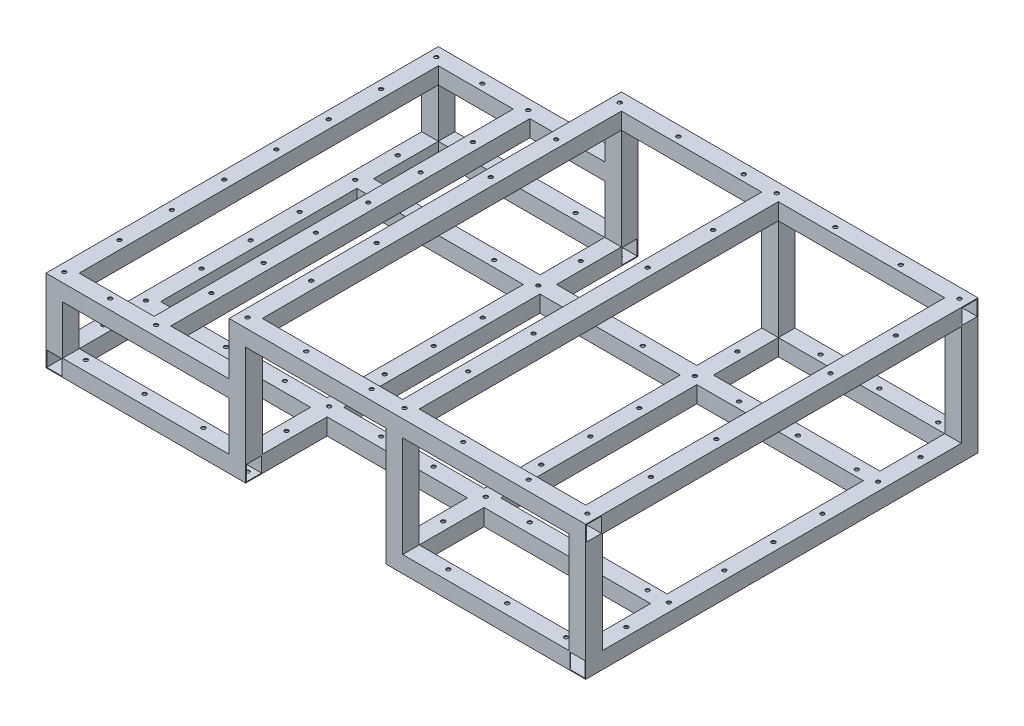
SolidWorks part; units mm, degrees
ref_plane "Front Plane" through (0, 0, 0) normal (0, 0, 1) x (1, 0, 0)
ref_plane "Top Plane" through (0, 0, 0) normal (0, 1, 0) x (1, 0, 0)
ref_plane "Right Plane" through (0, 0, 0) normal (1, 0, 0) x (0, 0, -1)
sketch "Sketch1" plane through (0, 0, 0) normal (0, 1, 0) x (1, 0, 0)
  line L0 (0, 0) -> (-415.7612, 0) construction
  line L1 (-387.3, -150) -> (387.3, -150)
  line L2 (-387.3, -150) -> (-387.3, -175.4)
  line L3 (-387.3, -175.4) -> (387.3, -175.4)
  line L4 (387.3, -150) -> (387.3, -175.4)
  line L9 (0, 0) -> (0, -321.173) construction
  line L10 (387.3, 150) -> (387.3, 175.4)
  line L11 (-387.3, 175.4) -> (387.3, 175.4)
  line L12 (-387.3, 150) -> (-387.3, 175.4)
  line L13 (-387.3, 150) -> (387.3, 150)
  point P7 (0, -175.4)
  dimension "D1" = 774.6
  dimension "D2" = 25.4
  dimension "D3" = 150
  dimension "D4" = 0
extrude "Boss-Extrude1" add sketch "Sketch1" along normal blind 25.4
sketch "Sketch4" plane through (-387.3, 0, 0) normal (-1, 0, 0) x (0, 0, 1)
  line L0 (-175.4, 25.4) -> (-150, 25.4) construction
  line L1 (-174.2, 24.2) -> (-151.2, 24.2)
  line L2 (-174.2, 24.2) -> (-174.2, 1.2)
  line L3 (-174.2, 1.2) -> (-151.2, 1.2)
  line L4 (-151.2, 24.2) -> (-151.2, 1.2)
  line L5 (-150, 25.4) -> (-150, 0) construction
  line L6 (-175.4, 0) -> (-150, 0) construction
  line L7 (-175.4, 25.4) -> (-175.4, 0) construction
  line L8 (0, 0) -> (0, 21.4103) construction
  line L9 (174.2, 1.2) -> (151.2, 1.2)
  line L10 (151.2, 24.2) -> (151.2, 1.2)
  line L11 (174.2, 24.2) -> (151.2, 24.2)
  line L12 (174.2, 24.2) -> (174.2, 1.2)
  dimension "D1" = 1.2
  dimension "D2" = 1.2
  dimension "D3" = 1.2
  dimension "D4" = 1.2
extrude "Cut-Extrude2" cut sketch "Sketch4" against normal up to next (774.6 mm away)
sketch "Sketch2" plane through (0, 0, 0) normal (0, -1, 0) x (1, 0, 0)
  line L0 (0, 0) -> (0, -349.2287) construction
  line L1 (412.7, 300) -> (387.3, 300)
  line L2 (412.7, 300) -> (412.7, -300)
  line L3 (412.7, -300) -> (387.3, -300)
  line L4 (387.3, 300) -> (387.3, -300)
  line L5 (0, 0) -> (432.1136, 0) construction
  line L6 (387.3, -150) -> (387.3, -175.4) construction
  line L7 (-387.3, 300) -> (-387.3, -300)
  line L8 (-412.7, -300) -> (-387.3, -300)
  line L9 (-412.7, 300) -> (-412.7, -300)
  line L10 (-412.7, 300) -> (-387.3, 300)
  point P10 (387.3, 0)
  dimension "D1" = 25.4
  dimension "D2" = 600
  dimension "D3" = 25.4
  dimension "D4" = 0
extrude "Boss-Extrude2" add sketch "Sketch2" against normal blind 25.4
sketch "Sketch3" plane through (0, 0, -300) normal (0, 0, -1) x (-1, 0, 0)
  line L0 (-387.3, 25.4) -> (-412.7, 25.4) construction
  line L1 (-411.5, 24.2) -> (-388.5, 24.2)
  line L2 (-411.5, 24.2) -> (-411.5, 1.2)
  line L3 (-411.5, 1.2) -> (-388.5, 1.2)
  line L4 (-388.5, 24.2) -> (-388.5, 1.2)
  line L5 (-387.3, 25.4) -> (-387.3, 0) construction
  line L6 (-387.3, 0) -> (-412.7, 0) construction
  line L7 (-412.7, 25.4) -> (-412.7, 0) construction
  line L8 (0, 0) -> (0, 119.739) construction
  line L9 (388.5, 24.2) -> (388.5, 1.2)
  line L10 (411.5, 1.2) -> (388.5, 1.2)
  line L11 (411.5, 24.2) -> (411.5, 1.2)
  line L12 (411.5, 24.2) -> (388.5, 24.2)
  point P10 (-400, 0)
  dimension "D1" = 1.2
  dimension "D2" = 1.2
  dimension "D3" = 1.2
  dimension "D4" = 1.2
extrude "Cut-Extrude1" cut sketch "Sketch3" against normal up to next
sketch "Sketch6" plane through (-387.3, 0, 0) normal (1, 0, 0) x (0, 0, -1)
  line L0 (300, 0) -> (175.4, 0) construction
  line L1 (300, 25.4) -> (274.6, 25.4)
  line L2 (300, 25.4) -> (300, 0)
  line L3 (300, 0) -> (274.6, 0)
  line L4 (274.6, 25.4) -> (274.6, 0)
  line L5 (0, 0) -> (0, 25.4) construction
  line L6 (150, 0) -> (-150, 0) construction
  line L7 (150, 25.4) -> (-150, 25.4) construction
  line L13 (-274.6, 25.4) -> (-274.6, 0)
  line L14 (-300, 0) -> (-274.6, 0)
  line L15 (-300, 25.4) -> (-300, 0)
  line L16 (-300, 25.4) -> (-274.6, 25.4)
  dimension "D1" = 25.4
extrude "Boss-Extrude3" add sketch "Sketch6" along normal blind 280
sketch "Sketch7" plane through (387.3, 0, 0) normal (-1, 0, 0) x (0, 0, 1)
  line L0 (-175.4, 25.4) -> (-300, 25.4) construction
  line L1 (-300, 0) -> (-274.6, 0)
  line L2 (-300, 0) -> (-300, 25.4)
  line L3 (-300, 25.4) -> (-274.6, 25.4)
  line L4 (-274.6, 0) -> (-274.6, 25.4)
  line L10 (0, 0) -> (0, 25.4) construction
  line L11 (150, 0) -> (-150, 0) construction
  line L12 (150, 25.4) -> (-150, 25.4) construction
  line L13 (274.6, 0) -> (274.6, 25.4)
  line L14 (300, 25.4) -> (274.6, 25.4)
  line L15 (300, 0) -> (300, 25.4)
  line L16 (300, 0) -> (274.6, 0)
  dimension "D1" = 25.4
extrude "Boss-Extrude4" add sketch "Sketch7" along normal blind 280
ref_plane "Plane1" through (0, 0, 0) normal (1, 0, 0) x (0, 0, -1)
sketch "Sketch8" plane through (0, 0, 0) normal (1, 0, 0) x (0, 0, -1)
  line L4 (-275.8, 24.2) -> (-298.8, 24.2)
  line L5 (-298.8, 24.2) -> (-298.8, 1.2)
  line L6 (-298.8, 1.2) -> (-275.8, 1.2)
  line L7 (-275.8, 1.2) -> (-275.8, 24.2)
  line L8 (-274.6, 25.4) -> (-300, 25.4)
  line L9 (-300, 25.4) -> (-300, 0)
  line L10 (-300, 0) -> (-274.6, 0)
  line L11 (-274.6, 0) -> (-274.6, 25.4)
  line L12 (-274.6, 25.4) -> (-300, 25.4)
  line L13 (-300, 25.4) -> (-300, 0)
  line L14 (-300, 0) -> (-274.6, 0)
  line L15 (-274.6, 0) -> (-274.6, 25.4)
  line L16 (300, 0) -> (300, 25.4)
  line L17 (300, 25.4) -> (274.6, 25.4)
  line L18 (274.6, 25.4) -> (274.6, 0)
  line L19 (274.6, 0) -> (300, 0)
  line L20 (300, 0) -> (300, 25.4)
  line L21 (300, 25.4) -> (274.6, 25.4)
  line L22 (274.6, 25.4) -> (274.6, 0)
  line L23 (274.6, 0) -> (300, 0)
  line L24 (298.8, 1.2) -> (298.8, 24.2)
  line L25 (298.8, 24.2) -> (275.8, 24.2)
  line L26 (275.8, 24.2) -> (275.8, 1.2)
  line L27 (275.8, 1.2) -> (298.8, 1.2)
  dimension "D1" = 0
  dimension "D2" = 0
  dimension "D3" = 1.2
  dimension "D4" = 1.2
extrude "Cut-Extrude4" cut sketch "Sketch8" against normal up to surface (388.5 mm away) and the other way up to vertex (388.5 mm away) contours L24 L25 L26 L27 | L7 L4 L5 L6 up to face at (-388.5, 12.7, 0) other way up to point (388.5, 1.2, 300)
sketch "Sketch9" plane through (0, 0, -274.6) normal (0, 0, 1) x (1, 0, 0)
  line L0 (-107.3, 25.4) -> (-387.3, 25.4) construction
  line L1 (-107.3, 0) -> (-132.7, 0)
  line L2 (-107.3, 0) -> (-107.3, 25.4)
  line L3 (-107.3, 25.4) -> (-132.7, 25.4)
  line L4 (-132.7, 0) -> (-132.7, 25.4)
  line L5 (-107.3, 0) -> (107.3, 0) construction
  line L6 (-107.3, 25.4) -> (107.3, 25.4) construction
  line L7 (0, 25.4) -> (0, 0) construction
  line L12 (-108.5, 1.2) -> (-131.5, 1.2)
  line L13 (-131.5, 1.2) -> (-131.5, 24.2)
  line L14 (-108.5, 24.2) -> (-131.5, 24.2)
  line L15 (-108.5, 1.2) -> (-108.5, 24.2)
  line L16 (108.5, 1.2) -> (108.5, 24.2)
  line L17 (108.5, 24.2) -> (131.5, 24.2)
  line L18 (107.3, 25.4) -> (132.7, 25.4)
  line L19 (107.3, 0) -> (107.3, 25.4)
  line L20 (131.5, 1.2) -> (131.5, 24.2)
  line L21 (108.5, 1.2) -> (131.5, 1.2)
  line L22 (132.7, 0) -> (132.7, 25.4)
  line L23 (107.3, 0) -> (132.7, 0)
  dimension "D1" = 25.4
  dimension "D2" = 1.2
extrude "Boss-Extrude5" add sketch "Sketch9" along normal up to surface (550.4 mm away) up to face at (-247.9, 12.7, 275.8)
sketch "Sketch11" plane through (0, 25.4, 0) normal (0, 1, 0) x (1, 0, 0)
  line L0 (-412.7, 0) -> (0, 0) construction
  line L1 (-412.7, 300) -> (-387.3, 300)
  line L2 (-412.7, 300) -> (-412.7, 274.6)
  line L3 (-412.7, 274.6) -> (-387.3, 274.6)
  line L4 (-387.3, 300) -> (-387.3, 274.6)
  line L5 (-412.7, -300) -> (-412.7, 300) construction
  line L7 (-411.5, 298.8) -> (-388.5, 298.8)
  line L8 (-388.5, 298.8) -> (-388.5, 275.8)
  line L9 (-411.5, 275.8) -> (-388.5, 275.8)
  line L10 (-411.5, 298.8) -> (-411.5, 275.8)
  line L11 (-411.5, -298.8) -> (-411.5, -275.8)
  line L12 (-411.5, -275.8) -> (-388.5, -275.8)
  line L13 (-388.5, -298.8) -> (-388.5, -275.8)
  line L14 (-411.5, -298.8) -> (-388.5, -298.8)
  line L15 (-387.3, -300) -> (-387.3, -274.6)
  line L16 (-412.7, -274.6) -> (-387.3, -274.6)
  line L17 (-412.7, -300) -> (-412.7, -274.6)
  line L18 (-412.7, -300) -> (-387.3, -300)
  dimension "D1" = 1.2
extrude "Boss-Extrude6" add sketch "Sketch11" along normal blind 74.6
sketch "Sketch12" plane through (0, 25.4, 0) normal (0, 1, 0) x (1, 0, 0)
  line L0 (-108.5, 298.8) -> (-131.5, 298.8)
  line L1 (-107.3, 300) -> (-132.7, 300)
  line L2 (-107.3, 300) -> (-107.3, 274.6)
  line L3 (-107.3, 274.6) -> (-132.7, 274.6)
  line L4 (-132.7, 300) -> (-132.7, 274.6)
  line L5 (-131.5, 298.8) -> (-131.5, 275.8)
  line L6 (-108.5, 275.8) -> (-131.5, 275.8)
  line L7 (-108.5, 298.8) -> (-108.5, 275.8)
  line L8 (-132.7, 0) -> (412.7, 0) construction
  line L10 (-132.7, -150) -> (-132.7, 150) construction
  line L11 (412.7, 300) -> (412.7, -300) construction
  line L12 (140, 0) -> (140, 300) construction
  line L13 (107.3, 300) -> (412.7, 300) construction
  line L14 (-108.5, -298.8) -> (-108.5, -275.8)
  line L15 (-108.5, -275.8) -> (-131.5, -275.8)
  line L16 (-131.5, -298.8) -> (-131.5, -275.8)
  line L17 (-132.7, -300) -> (-132.7, -274.6)
  line L18 (-107.3, -274.6) -> (-132.7, -274.6)
  line L19 (-107.3, -300) -> (-107.3, -274.6)
  line L20 (-107.3, -300) -> (-132.7, -300)
  line L21 (-108.5, -298.8) -> (-131.5, -298.8)
  line L22 (388.5, -298.8) -> (411.5, -298.8)
  line L23 (387.3, -300) -> (412.7, -300)
  line L24 (387.3, -300) -> (387.3, -274.6)
  line L25 (387.3, -274.6) -> (412.7, -274.6)
  line L26 (412.7, -300) -> (412.7, -274.6)
  line L27 (411.5, -298.8) -> (411.5, -275.8)
  line L28 (388.5, -275.8) -> (411.5, -275.8)
  line L29 (388.5, -298.8) -> (388.5, -275.8)
  line L30 (388.5, 298.8) -> (388.5, 275.8)
  line L31 (388.5, 275.8) -> (411.5, 275.8)
  line L32 (411.5, 298.8) -> (411.5, 275.8)
  line L33 (412.7, 300) -> (412.7, 274.6)
  line L34 (387.3, 274.6) -> (412.7, 274.6)
  line L35 (387.3, 300) -> (387.3, 274.6)
  line L36 (387.3, 300) -> (412.7, 300)
  line L37 (388.5, 298.8) -> (411.5, 298.8)
  line L38 (132.7, 274.6) -> (387.3, 274.6) construction
  line L39 (107.3, 300) -> (132.7, 300)
  line L40 (107.3, 300) -> (107.3, 274.6)
  line L41 (107.3, 274.6) -> (132.7, 274.6)
  line L42 (132.7, 300) -> (132.7, 274.6)
  line L47 (108.5, 298.8) -> (131.5, 298.8)
  line L48 (131.5, 298.8) -> (131.5, 275.8)
  line L49 (108.5, 275.8) -> (131.5, 275.8)
  line L50 (108.5, 298.8) -> (108.5, 275.8)
  line L51 (108.5, -298.8) -> (108.5, -275.8)
  line L52 (108.5, -275.8) -> (131.5, -275.8)
  line L53 (131.5, -298.8) -> (131.5, -275.8)
  line L54 (108.5, -298.8) -> (131.5, -298.8)
  line L55 (132.7, -300) -> (132.7, -274.6)
  line L56 (107.3, -274.6) -> (132.7, -274.6)
  line L57 (107.3, -300) -> (107.3, -274.6)
  line L58 (107.3, -300) -> (132.7, -300)
  line L59 (107.3, 175.4) -> (107.3, 300) construction
  point P12 (387.3, 287.3)
  dimension "D2" = 0
  dimension "D3" = 25.4
  dimension "D5" = 254.6
  dimension "D6" = 214.6
  dimension "D1" = 1.2
  dimension "D4" = 1.2
extrude "Boss-Extrude7" add sketch "Sketch12" along normal blind 154.6
sketch "Sketch13" plane through (0, 180, 0) normal (0, 1, 0) x (1, 0, 0)
  line L0 (-107.3, 274.6) -> (-107.3, -274.6) construction
  line L1 (-132.7, -300) -> (412.7, -300)
  line L2 (-132.7, -300) -> (-132.7, -274.6)
  line L3 (-132.7, -274.6) -> (412.7, -274.6)
  line L4 (412.7, -300) -> (412.7, -274.6)
  line L5 (-107.3, 0) -> (0, 0) construction
  line L6 (412.7, 300) -> (412.7, 274.6)
  line L7 (-132.7, 274.6) -> (412.7, 274.6)
  line L8 (-132.7, 300) -> (-132.7, 274.6)
  line L9 (-132.7, 300) -> (412.7, 300)
extrude "Boss-Extrude9" add sketch "Sketch13" along normal blind 25.4
sketch "Sketch14" plane through (-132.7, 0, 0) normal (-1, 0, 0) x (0, 0, 1)
  line L0 (-300, 205.4) -> (-274.6, 205.4) construction
  line L1 (-298.8, 204.2) -> (-275.8, 204.2)
  line L2 (-298.8, 204.2) -> (-298.8, 181.2)
  line L3 (-298.8, 181.2) -> (-275.8, 181.2)
  line L4 (-275.8, 204.2) -> (-275.8, 181.2)
  line L5 (-300, 205.4) -> (-300, 25.4) construction
  line L6 (-274.6, 205.4) -> (-274.6, 25.4) construction
  line L7 (-300, 180) -> (-274.6, 180) construction
  line L8 (-274.6, 180) -> (274.6, 180) construction
  line L9 (274.6, 205.4) -> (274.6, 25.4) construction
  line L10 (0, 180) -> (0, 204.2) construction
  line L11 (300, 180) -> (274.6, 180) construction
  line L12 (275.8, 204.2) -> (275.8, 181.2)
  line L13 (298.8, 181.2) -> (275.8, 181.2)
  line L14 (298.8, 204.2) -> (298.8, 181.2)
  line L15 (298.8, 204.2) -> (275.8, 204.2)
  dimension "D1" = 1.2
  dimension "D2" = 1.2
  dimension "D3" = 1.2
  dimension "D4" = 25.4
  dimension "D5" = 1.2
extrude "Cut-Extrude5" cut sketch "Sketch14" against normal up to surface (545.4 mm away)
sketch "Sketch15" plane through (0, 0, -274.6) normal (0, 0, 1) x (1, 0, 0)
  line L27 (107.3, 180) -> (132.7, 180)
  line L28 (132.7, 180) -> (132.7, 205.4)
  line L29 (-132.7, 205.4) -> (412.7, 205.4) construction
  line L30 (132.7, 205.4) -> (107.3, 205.4)
  line L31 (107.3, 205.4) -> (107.3, 180)
  line L32 (108.5, 181.2) -> (131.5, 181.2)
  line L33 (131.5, 181.2) -> (131.5, 204.2)
  line L34 (131.5, 204.2) -> (108.5, 204.2)
  line L35 (108.5, 204.2) -> (108.5, 181.2)
  line L36 (-107.3, 180) -> (-107.3, 25.4) construction
  line L37 (-132.7, 205.4) -> (-107.3, 205.4)
  line L38 (-132.7, 205.4) -> (-132.7, 180)
  line L39 (-132.7, 180) -> (-107.3, 180)
  line L40 (-107.3, 205.4) -> (-107.3, 180)
  line L41 (-131.5, 204.2) -> (-108.5, 204.2)
  line L42 (412.7, 205.4) -> (387.3, 205.4)
  line L43 (412.7, 205.4) -> (412.7, 180)
  line L44 (412.7, 180) -> (387.3, 180)
  line L45 (387.3, 205.4) -> (387.3, 180)
  line L46 (-108.5, 204.2) -> (-108.5, 181.2)
  line L47 (-131.5, 181.2) -> (-108.5, 181.2)
  line L48 (-131.5, 204.2) -> (-131.5, 181.2)
  line L49 (411.5, 204.2) -> (388.5, 204.2)
  line L50 (388.5, 204.2) -> (388.5, 181.2)
  line L51 (411.5, 181.2) -> (388.5, 181.2)
  line L52 (411.5, 204.2) -> (411.5, 181.2)
  dimension "D2" = 1.2
  dimension "D1" = 1.2
extrude "Boss-Extrude10" add sketch "Sketch15" along normal up to surface (549.2 mm away) up to face at (260, 12.7, 274.6)
sketch "Sketch16" plane through (-412.7, 0, 0) normal (-1, 0, 0) x (0, 0, 1)
  line L0 (275.8, 101.2) -> (298.8, 101.2)
  line L1 (274.6, 100) -> (300, 100)
  line L2 (274.6, 100) -> (274.6, 125.4)
  line L3 (274.6, 125.4) -> (300, 125.4)
  line L4 (300, 100) -> (300, 125.4)
  line L5 (298.8, 101.2) -> (298.8, 124.2)
  line L6 (275.8, 124.2) -> (298.8, 124.2)
  line L7 (275.8, 101.2) -> (275.8, 124.2)
  line L8 (-274.6, 100) -> (274.6, 100) construction
  line L9 (0, 100) -> (0, 0) construction
  line L11 (300, 0) -> (-300, 0) construction
  line L12 (-275.8, 101.2) -> (-275.8, 124.2)
  line L13 (-275.8, 124.2) -> (-298.8, 124.2)
  line L14 (-298.8, 101.2) -> (-298.8, 124.2)
  line L15 (-300, 100) -> (-300, 125.4)
  line L16 (-274.6, 125.4) -> (-300, 125.4)
  line L17 (-274.6, 100) -> (-274.6, 125.4)
  line L18 (-274.6, 100) -> (-300, 100)
  line L19 (-275.8, 101.2) -> (-298.8, 101.2)
  dimension "D1" = 25.4
  dimension "D2" = 25.4
  dimension "D3" = 1.2
extrude "Boss-Extrude11" add sketch "Sketch16" against normal up to surface (280 mm away)
sketch "Sketch17" plane through (0, 0, 274.6) normal (0, 0, -1) x (-1, 0, 0)
  line L0 (132.7, 100) -> (387.3, 100) construction
  line L1 (387.3, 100) -> (412.7, 100)
  line L2 (387.3, 100) -> (387.3, 125.4)
  line L3 (387.3, 125.4) -> (412.7, 125.4)
  line L4 (412.7, 100) -> (412.7, 125.4)
  line L5 (260, 100) -> (260, 125.4) construction
  line L7 (248.5, 124.2) -> (271.5, 124.2)
  line L8 (247.3, 125.4) -> (272.7, 125.4)
  line L9 (247.3, 125.4) -> (247.3, 100)
  line L10 (247.3, 100) -> (272.7, 100)
  line L11 (272.7, 125.4) -> (272.7, 100)
  line L12 (271.5, 124.2) -> (271.5, 101.2)
  line L13 (248.5, 101.2) -> (271.5, 101.2)
  line L14 (248.5, 124.2) -> (248.5, 101.2)
  line L15 (-132.7, 25.4) -> (-132.7, 0) construction
  line L16 (388.5, 101.2) -> (411.5, 101.2)
  line L17 (411.5, 101.2) -> (411.5, 124.2)
  line L18 (388.5, 124.2) -> (411.5, 124.2)
  line L19 (388.5, 101.2) -> (388.5, 124.2)
  line L20 (-132.7, 25.4) -> (-387.3, 25.4) construction
  dimension "D1" = 380
  dimension "D2" = 381.2
  dimension "D3" = 392.7
  dimension "D4" = 404.2
  dimension "D5" = 520
  dimension "D6" = 521.2
  dimension "D7" = 74.6
  dimension "D8" = 75.8
extrude "Boss-Extrude12" add sketch "Sketch17" along normal up to surface (549.2 mm away) up to face at (260, 12.7, -274.6)
sketch "Sketch18" plane through (0, 25.4, 0) normal (0, 1, 0) x (1, 0, 0)
  line L0 (132.7, 274.6) -> (387.3, 274.6) construction
  line L1 (387.3, 300) -> (387.3, 274.6) construction
  line L2 (132.7, 274.6) -> (387.3, 274.6) construction
  line L3 (107.3, 175.4) -> (107.3, 274.6) construction
  line L4 (387.3, -150) -> (387.3, 150) construction
  line L5 (132.7, 150) -> (387.3, 150) construction
  line L6 (107.3, -150) -> (107.3, 150) construction
  line L7 (412.7, 0) -> (0, 0) construction
  line L8 (412.7, 274.6) -> (412.7, -274.6) construction
  line L9 (0, 0) -> (0, 303.2716) construction
  line L11 (387.3, 175.4) -> (387.3, 274.6) construction
  line L12 (388.5, 300) -> (411.5, 300) construction
  line L13 (411.5, 300) -> (388.5, 300) construction
  line L14 (107.3, 300) -> (412.7, 300) construction
  line L15 (-107.3, 150) -> (107.3, 150) construction
  line L16 (132.7, 300) -> (387.3, 300) construction
  circle A0 centre (367.3, 284.6) radius 3
  circle A1 centre (277.3, 284.6) radius 3
  circle A2 centre (187.3, 284.6) radius 3
  circle A3 centre (119.8, 284.6) radius 3
  circle A4 centre (367.3, 160) radius 3
  circle A5 centre (277.3, 160) radius 3
  circle A6 centre (187.3, 160) radius 3
  circle A7 centre (119.8, 160) radius 3
  circle A8 centre (119.8, 225) radius 3
  circle A9 centre (399.8, 225) radius 3
  circle A11 centre (399.8, 0) radius 3
  circle A12 centre (399.8, 75) radius 3
  circle A13 centre (119.8, 0) radius 3
  circle A14 centre (119.8, 75) radius 3
  circle A15 centre (399.8, 160) radius 3
  circle A16 centre (40, 160) radius 3
  circle A17 centre (-40, 160) radius 3
  circle A18 centre (-399.8, 160) radius 3
  circle A19 centre (-119.8, 75) radius 3
  circle A20 centre (-119.8, 0) radius 3
  circle A21 centre (-399.8, 75) radius 3
  circle A22 centre (-399.8, 0) radius 3
  circle A23 centre (-399.8, 225) radius 3
  circle A24 centre (-119.8, 225) radius 3
  circle A25 centre (-119.8, 160) radius 3
  circle A26 centre (-187.3, 160) radius 3
  circle A27 centre (-277.3, 160) radius 3
  circle A28 centre (-367.3, 160) radius 3
  circle A29 centre (-119.8, 284.6) radius 3
  circle A30 centre (-187.3, 284.6) radius 3
  circle A31 centre (-277.3, 284.6) radius 3
  circle A32 centre (-367.3, 284.6) radius 3
  circle A33 centre (-367.3, -284.6) radius 3
  circle A34 centre (-277.3, -284.6) radius 3
  circle A35 centre (-187.3, -284.6) radius 3
  circle A36 centre (-119.8, -284.6) radius 3
  circle A37 centre (-367.3, -160) radius 3
  circle A38 centre (-277.3, -160) radius 3
  circle A39 centre (-187.3, -160) radius 3
  circle A40 centre (-119.8, -160) radius 3
  circle A41 centre (-119.8, -225) radius 3
  circle A42 centre (-399.8, -225) radius 3
  circle A43 centre (-399.8, -75) radius 3
  circle A44 centre (-119.8, -75) radius 3
  circle A45 centre (-399.8, -160) radius 3
  circle A46 centre (-40, -160) radius 3
  circle A47 centre (40, -160) radius 3
  circle A48 centre (399.8, -160) radius 3
  circle A49 centre (119.8, -75) radius 3
  circle A50 centre (399.8, -75) radius 3
  circle A51 centre (399.8, -225) radius 3
  circle A52 centre (119.8, -225) radius 3
  circle A53 centre (119.8, -160) radius 3
  circle A54 centre (187.3, -160) radius 3
  circle A55 centre (277.3, -160) radius 3
  circle A56 centre (367.3, -160) radius 3
  circle A57 centre (119.8, -284.6) radius 3
  circle A58 centre (187.3, -284.6) radius 3
  circle A59 centre (277.3, -284.6) radius 3
  circle A60 centre (367.3, -284.6) radius 3
  dimension "D1" = 10
  dimension "D5" = 6
  dimension "D6" = 6
  dimension "D7" = 10
  dimension "D9" = 6
  dimension "D10" = 6
  dimension "D13" = 6
  dimension "D14" = 6
  dimension "D15" = 6
  dimension "D22" = 6
  dimension "D27" = 6
  dimension "D28" = 6
  dimension "D29" = 12.5
  dimension "D30" = 75
  dimension "D33" = 6
  dimension "D34" = 6
  dimension "D35" = 6
  dimension "D36" = 6
  dimension "D43" = 6
  dimension "D44" = 12.5
  dimension "D46" = 6
  dimension "D2" = 20
  dimension "D3" = 10
  dimension "D4" = 110
  dimension "D8" = 200
  dimension "D11" = 10
  dimension "D12" = 12.5
  dimension "D16" = 20
  dimension "D17" = 10
  dimension "D18" = 110
  dimension "D19" = 10
  dimension "D20" = 10
  dimension "D21" = 200
  dimension "D23" = 10
  dimension "D24" = 12.5
  dimension "D25" = 12.5
  dimension "D26" = 75
  dimension "D31" = 12.5
  dimension "D32" = 300
  dimension "D37" = 12.5
  dimension "D38" = 12.5
  dimension "D39" = 225
  dimension "D40" = 300
  dimension "D41" = 225
  dimension "D42" = 12.5
  dimension "D45" = 10
  dimension "D47" = 10
  dimension "D48" = 40
extrude "Cut-Extrude6" cut sketch "Sketch18" against normal up to surface (25.4 mm away) up to face at (0, 0, 0)
sketch "Sketch20" plane through (0, 205.4, 0) normal (0, 1, 0) x (1, 0, 0)
  line L0 (387.3, 0) -> (132.7, 0) construction
  line L4 (140, 300) -> (140, -300) construction
  line L6 (260, 274.6) -> (260, 0) construction
  line L8 (260, 137.3) -> (387.3, 137.3) construction
  line L10 (387.3, -274.6) -> (387.3, 274.6) construction
  circle A0 centre (399.8, 284.6) radius 3
  circle A2 centre (399.8, 187.3) radius 3
  circle A3 centre (310, 284.6) radius 3
  circle A4 centre (210, 284.6) radius 3
  circle A5 centre (120.2, 187.3) radius 3
  circle A6 centre (120.2, 284.6) radius 3
  circle A7 centre (120.2, 87.3) radius 3
  circle A8 centre (399.8, 87.3) radius 3
  circle A9 centre (399.8, -87.3) radius 3
  circle A10 centre (120.2, -87.3) radius 3
  circle A11 centre (120.2, -284.6) radius 3
  circle A12 centre (120.2, -187.3) radius 3
  circle A13 centre (210, -284.6) radius 3
  circle A14 centre (310, -284.6) radius 3
  circle A15 centre (399.8, -187.3) radius 3
  circle A16 centre (399.8, -284.6) radius 3
  circle A17 centre (-119.8, -284.6) radius 3
  circle A18 centre (-119.8, -187.3) radius 3
  circle A19 centre (-30, -284.6) radius 3
  circle A20 centre (70, -284.6) radius 3
  circle A21 centre (-119.8, -87.3) radius 3
  circle A22 centre (-119.8, 87.3) radius 3
  circle A23 centre (70, 284.6) radius 3
  circle A24 centre (-30, 284.6) radius 3
  circle A25 centre (-119.8, 187.3) radius 3
  circle A26 centre (-119.8, 284.6) radius 3
  dimension "D1" = 6
  dimension "D6" = 247.3
  dimension "D7" = 267.1
  dimension "D2" = 12.5
  dimension "D3" = 77.3
  dimension "D4" = 127.3
  dimension "D5" = 177.3
  dimension "D8" = 317.3
  dimension "D9" = 417.3
  dimension "D10" = 507.1
  dimension "D11" = 87.3
  dimension "D12" = 187.3
  dimension "D13" = 274.6
  dimension "D14" = 361.9
  dimension "D15" = 411.9
  dimension "D16" = 461.9
  dimension "D17" = 559.2
  dimension "D18" = 10
extrude "Cut-Extrude7" cut sketch "Sketch20" against normal up to next (1.2 mm away)
sketch "Sketch21" plane through (0, 125.4, 0) normal (0, 1, 0) x (1, 0, 0)
  line L0 (-272.7, 0) -> (-387.3, 0) construction
  line L1 (-272.7, 274.6) -> (-272.7, -274.6) construction
  line L2 (-387.3, 274.6) -> (-387.3, -274.6) construction
  line L3 (-330, 274.6) -> (-330, 0) construction
  line L4 (-272.7, 274.6) -> (-387.3, 274.6) construction
  line L5 (-412.7, -300) -> (-412.7, 300) construction
  line L6 (-132.7, 300) -> (-412.7, 300) construction
  circle A0 centre (-400.2, 284.6) radius 3
  circle A1 centre (-329.995, 284.6) radius 3
  circle A2 centre (-400.2, 200) radius 3
  circle A3 centre (-400.2, 120) radius 3
  circle A4 centre (-400.2, 40) radius 3
  circle A5 centre (-259.8, 40) radius 3
  circle A6 centre (-259.8, 120) radius 3
  circle A7 centre (-259.8, 200) radius 3
  circle A8 centre (-259.8, 284.6) radius 3
  circle A9 centre (-259.8, -284.6) radius 3
  circle A10 centre (-259.8, -200) radius 3
  circle A11 centre (-259.8, -120) radius 3
  circle A12 centre (-400.2, -40) radius 3
  circle A13 centre (-400.2, -120) radius 3
  circle A14 centre (-400.2, -200) radius 3
  circle A15 centre (-329.995, -284.6) radius 3
  circle A16 centre (-400.2, -284.6) radius 3
  circle A17 centre (-259.8, -40) radius 3
  dimension "D1" = 12.5
  dimension "D3" = 6
  dimension "D4" = 6
  dimension "D5" = 10
  dimension "D8" = 6
  dimension "D9" = 6
  dimension "D13" = 12.5
  dimension "D14" = 6
  dimension "D2" = 10
  dimension "D6" = 0.01
  dimension "D7" = 12.5
  dimension "D10" = 12.5
  dimension "D11" = 100
  dimension "D12" = 120
  dimension "D15" = 40
extrude "Cut-Extrude8" cut sketch "Sketch21" against normal up to next
equation "\"thi\"=1.2"
equation "\"D5@Sketch14\"=\"thi\""
equation "\"D2@Sketch14\"=\"thi\""
equation "\"D3@Sketch14\"=\"thi\""
equation "\"D1@Sketch14\"=\"thi\""
